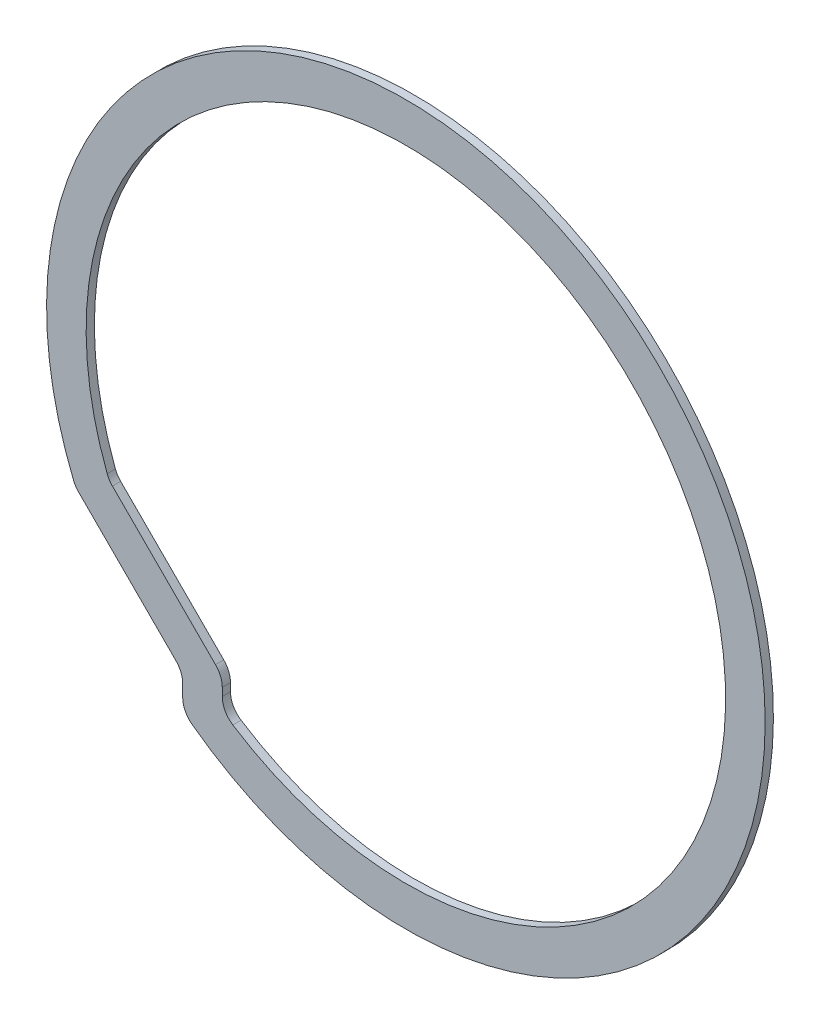
SolidWorks part; units mm, degrees
material "Balsa"
ref_plane "Front Plane" through (0, 0, 0) normal (0, 0, 1) x (1, 0, 0)
ref_plane "Top Plane" through (0, 0, 0) normal (0, 1, 0) x (1, 0, 0)
ref_plane "Right Plane" through (0, 0, 0) normal (1, 0, 0) x (0, 0, -1)
sketch "Sketch1" plane through (0, 0, 0) normal (0, 0, 1) x (1, 0, 0)
  line L0 (0, 32.094) -> (0, -346.2619) construction
  line L1 (0, 0) -> (0, 244.345) construction
  line L2 (0, 0) -> (0, 471.6969) construction
  line L3 (0, 0) -> (-283.5939, 0) construction
  line L4 (-127.2933, -32.5553) -> (-85.9841, -73.8644)
  line L5 (-85.9841, -73.8644) -> (-85.9841, -86.6438)
  line L6 (-85.9841, -73.8644) -> (-54.3993, -105.4493) construction
  arc A0 (-54.3993, -105.4493) -> (-127.2933, -32.5553) centre (0, 21.844) ccw
  arc A2 (-82.075, -89.6305) -> (-54.3993, -105.4493) centre (0, 21.844) ccw construction
  arc A3 (-127.2933, -32.5553) -> (-82.075, -89.6305) centre (0, 21.844) ccw construction
  arc A4 (-85.9841, -86.6438) -> (-54.3993, -105.4493) centre (0, 21.844) ccw
  spline S2 degree 3 poles (-1530.9406, -7642.7149) (259.0907, -1408.3953) (378.6573, 10.519) (49.9381, 150.9258) (45.7097, 152.4909) (37.1079, 155.2035) (32.7346, 156.3511) (27.1752, 157.5183) (26.0587, 157.7384) (23.8163, 158.1514) (22.6888, 158.3447) (19.306, 158.8811) (17.0511, 159.1813) (10.2867, 159.9126) (1.2693, 160.4377) (-7.745, 160.0789) (-14.5046, 159.4749) (-16.7575, 159.2176) (-20.1367, 158.7464) (-21.263, 158.5751) (-23.5156, 158.2037) (-24.6421, 158.0036) (-30.2426, 156.9366) (-34.6466, 155.8674) (-43.3063, 153.3113) (-47.562, 151.8242) (-55.9254, 148.4331) (-60.0331, 146.529) (-66.0807, 143.3516) (-68.0818, 142.2359) (-72.0044, 139.9197) (-73.9301, 138.7173) (-79.6017, 134.9792) (-86.884, 129.6473) (-93.6143, 123.6295) (-98.4521, 118.8554) (-100.0296, 117.2204) (-102.3424, 114.7015) (-103.1054, 113.8496) (-104.6077, 112.1297) (-105.3467, 111.2623) (-108.9818, 106.8875) (-111.6981, 103.2683) (-116.7574, 95.7975) (-119.1004, 91.9459) (-123.4121, 84.0098) (-125.3809, 79.9253) (-127.6006, 74.6695) (-128.0327, 73.61) (-128.8681, 71.4874) (-129.2719, 70.423) (-130.4422, 67.2205) (-131.1674, 65.0732) (-133.1812, 58.5951) (-135.4347, 49.861) (-136.834, 40.9354) (-137.5569, 34.168) (-137.7434, 31.9) (-137.9397, 28.4793) (-137.9911, 27.3374) (-138.0656, 25.0596) (-138.0887, 23.9223) (-138.135, 18.2442) (-137.9496, 13.7276) (-137.1441, 4.7454) (-136.5239, 0.2797) (-134.8456, -8.6005) (-133.7876, -13.015) (-131.2181, -21.791) (-129.7278, -26.0794) (-126.351, -34.4622) (-124.4643, -38.5569) (-120.2966, -46.5538) (-118.0156, -50.456) (-114.9122, -55.2108) (-114.2789, -56.1556) (-112.9868, -58.0327) (-112.3272, -58.9661) (-110.315, -61.7398) (-108.9333, -63.5482) (-104.6702, -68.8537) (-98.6716, -75.6089) (-92.0553, -81.7381) (-86.8592, -86.0978) (-85.0881, -87.5114) (-82.3719, -89.5716) (-81.4566, -90.2482) (-79.6058, -91.5811) (-78.6696, -92.238) (312.7351, -359.6403) (1980.7618, 1435.5712) (5240.7041, 5800.1077) knots -2.409432 -2.409432 -2.409432 -2.409432 0.03125 0.03125 0.0625 0.0625 0.09375 0.09375 0.101563 0.101563 0.109375 0.109375 0.125 0.125 0.15625 0.1875 0.1875 0.203125 0.203125 0.210937 0.210937 0.21875 0.21875 0.25 0.25 0.28125 0.28125 0.3125 0.3125 0.328125 0.328125 0.34375 0.34375 0.375 0.40625 0.40625 0.421875 0.421875 0.429687 0.429687 0.4375 0.4375 0.46875 0.46875 0.5 0.5 0.53125 0.53125 0.539062 0.539062 0.546875 0.546875 0.5625 0.5625 0.59375 0.625 0.625 0.640625 0.640625 0.648437 0.648437 0.65625 0.65625 0.6875 0.6875 0.71875 0.71875 0.75 0.75 0.78125 0.78125 0.8125 0.8125 0.84375 0.84375 0.851562 0.851562 0.859375 0.859375 0.875 0.875 0.90625 0.9375 0.9375 0.953125 0.953125 0.960937 0.960937 0.96875 0.96875 4.2021 4.2021 4.2021 4.2021 only from (66.3397, 143.1887) to (-66.0465, -100.0388)
  spline S3 degree 3 poles (66.3397, 143.1887) (62.3323, 145.3909) (58.2494, 147.3758) (49.9381, 150.9258) (45.7097, 152.4909) (37.1079, 155.2035) (32.7346, 156.3511) (27.1752, 157.5183) (26.0587, 157.7384) (23.8163, 158.1514) (22.6888, 158.3447) (19.306, 158.8811) (17.0511, 159.1813) (10.2867, 159.9126) (1.2693, 160.4377) (-7.745, 160.0789) (-14.5046, 159.4749) (-16.7575, 159.2176) (-20.1367, 158.7464) (-21.263, 158.5751) (-23.5156, 158.2037) (-24.6421, 158.0036) (-30.2426, 156.9366) (-34.6466, 155.8674) (-43.3063, 153.3113) (-47.562, 151.8242) (-55.9254, 148.4331) (-60.0331, 146.529) (-66.0807, 143.3516) (-68.0818, 142.2359) (-72.0044, 139.9197) (-73.9301, 138.7173) (-79.6017, 134.9792) (-86.884, 129.6473) (-93.6143, 123.6295) (-98.4521, 118.8554) (-100.0296, 117.2204) (-102.3424, 114.7015) (-103.1054, 113.8496) (-104.6077, 112.1297) (-105.3467, 111.2623) (-108.9818, 106.8875) (-111.6981, 103.2683) (-116.7574, 95.7975) (-119.1004, 91.9459) (-123.4121, 84.0098) (-125.3809, 79.9253) (-127.6006, 74.6695) (-128.0327, 73.61) (-128.8681, 71.4874) (-129.2719, 70.423) (-130.4422, 67.2205) (-131.1674, 65.0732) (-133.1812, 58.5951) (-135.4347, 49.861) (-136.834, 40.9354) (-137.5569, 34.168) (-137.7434, 31.9) (-137.9397, 28.4793) (-137.9911, 27.3374) (-138.0656, 25.0596) (-138.0887, 23.9223) (-138.135, 18.2442) (-137.9496, 13.7276) (-137.1441, 4.7454) (-136.5239, 0.2797) (-134.8456, -8.6005) (-133.7876, -13.015) (-131.2181, -21.791) (-129.7278, -26.0794) (-127.6847, -31.1513) (-127.3213, -32.0275) (-126.9491, -32.8995) knots 0 0 0 0 0.03125 0.03125 0.0625 0.0625 0.09375 0.09375 0.101563 0.101563 0.109375 0.109375 0.125 0.125 0.15625 0.1875 0.1875 0.203125 0.203125 0.210937 0.210937 0.21875 0.21875 0.25 0.25 0.28125 0.28125 0.3125 0.3125 0.328125 0.328125 0.34375 0.34375 0.375 0.40625 0.40625 0.421875 0.421875 0.429687 0.429687 0.4375 0.4375 0.46875 0.46875 0.5 0.5 0.53125 0.53125 0.539062 0.539062 0.546875 0.546875 0.5625 0.5625 0.59375 0.625 0.625 0.640625 0.640625 0.648437 0.648437 0.65625 0.65625 0.6875 0.6875 0.71875 0.71875 0.75 0.75 0.78125 0.78125 0.787815 0.787815 0.787815 0.787815 construction
  point P2 (0, 160.2226)
  point P3 (0, -116.9127)
  point P23 (-85.9841, -73.8644)
  dimension "D1" = 277.1353
  dimension "D2" = 276.86
  dimension "D3" = 21.844
  dimension "D5" = 45
  dimension "D6" = 113.03
  dimension "D4" = 58.42
  dimension "D7" = 45
extrude "Boss-Extrude1" add sketch "Sketch1" along normal mid plane 3.175
sketch "Sketch2" plane through (0, 0, 1.5875) normal (0, 0, 1) x (1, 0, 0)
  line L4 (-114.3729, -23.9231) -> (-70.7441, -67.5518)
  line L5 (-70.7441, -67.5518) -> (-70.7441, -79.0076)
  line L6 (-114.3729, -23.9231) -> (-70.7441, -67.5518)
  line L7 (-70.7441, -67.5518) -> (-70.7441, -79.0076)
  arc A2 (-70.7441, -79.0076) -> (-114.3729, -23.9231) centre (0, 21.844) ccw
  arc A3 (-70.7441, -79.0076) -> (-114.3729, -23.9231) centre (0, 21.844) ccw
  dimension "D1" = 15.24
extrude "Cut-Extrude1" cut sketch "Sketch2" against normal up to surface (3.175 mm away) up to face at (-27.5361, -9.1994, -1.5875)
fillet "Fillet1" radius 8.89 6 edges at (-127.2933, -32.5553, 0) (-114.3729, -23.9231, 0) (-85.9841, -73.8644, 0) (-85.9841, -86.6438, 0) (-70.7441, -67.5518, 0) (-70.7441, -79.0076, 0)
sketch "Sketch3" plane through (0, 0, 1.5875) normal (0, 0, 1) x (1, 0, 0)
  line L0 (-0.0002, 49.9919) -> (-0.0176, 733.2) construction
  line L1 (-0.0002, 49.9919) -> (-0.0176, 733.2) construction
  line L2 (-136.2041, -28.3557) -> (-0.0002, 49.9919) construction
  line L3 (136.2076, -28.3488) -> (-0.0002, 49.9919) construction
  line L4 (-136.2041, -28.3557) -> (-0.0002, 49.9919) construction
  line L5 (136.2076, -28.3488) -> (-0.0002, 49.9919) construction
  line L6 (-1.6539, 152.6441) -> (-1.654, 160.2641)
  line L7 (1.6481, 152.6442) -> (1.648, 160.2642)
  line L8 (-1.6539, 152.6441) -> (1.6481, 152.6442)
  line L9 (119.8485, -45.962) -> (106.7537, -38.3747)
  line L10 (121.4435, -43.2066) -> (108.3479, -35.6188)
  line L11 (-126.0584, -33.7901) -> (-88.588, -71.2606)
  line L12 (-85.9841, -77.5468) -> (-85.9841, -82.2574)
  line L13 (-126.0584, -33.7901) -> (-88.588, -71.2606) construction
  line L14 (-85.9841, -77.5468) -> (-85.9841, -82.2574) construction
  line L18 (121.4435, -43.2066) -> (108.3479, -35.6188)
  line L30 (-123.167, -47.8929) -> (-106.3545, -38.1503)
  line L35 (119.8485, -45.962) -> (106.7537, -38.3747)
  line L47 (108.5244, -35.721) -> (120.1169, -46.1175) construction
  line L48 (114.3206, -40.9193) -> (126.5619, -48.0121) construction
  line L49 (113.8577, -42.5592) -> (122.0137, -47.2849)
  line L50 (115.5132, -39.7021) -> (123.6691, -44.4278)
  line L51 (113.8577, -42.5592) -> (115.5132, -39.7021)
  line L52 (122.0137, -47.2849) -> (123.6691, -44.4278)
  line L58 (-124.7703, -45.1423) -> (-107.9499, -35.3951)
  line L59 (-124.7703, -45.1423) -> (-123.167, -47.8929)
  line L71 (-124.7703, -45.1423) -> (-123.167, -47.8929) construction
  line L72 (-124.7703, -45.1423) -> (-107.9499, -35.3951) construction
  line L73 (-123.167, -47.8929) -> (-106.3545, -38.1503) construction
  line L74 (-123.167, -47.8929) -> (-107.9499, -35.3951) construction
  line L75 (-115.5584, -41.644) -> (-110.9064, -38.9482) construction
  line L76 (-119.3826, -41.9518) -> (-112.6266, -38.0369)
  line L77 (-117.727, -44.8088) -> (-110.971, -40.8938)
  line L78 (-119.3826, -41.9518) -> (-117.727, -44.8088)
  line L79 (-112.6266, -38.0369) -> (-110.971, -40.8938)
  arc A0 (-54.3993, -105.4493) -> (-127.2933, -32.5553) centre (0, 21.844) ccw construction
  arc A2 (-1.654, 160.2641) -> (-130.2816, -24.9489) centre (0, 21.844) ccw construction
  arc A3 (-130.2816, -24.9489) -> (-127.2933, -32.5553) centre (0, 21.844) ccw construction
  arc A4 (-1.654, 160.2641) -> (-130.2816, -24.9489) centre (0, 21.844) ccw construction
  arc A5 (-130.2816, -24.9489) -> (-127.9919, -30.8906) centre (0, 21.844) ccw construction
  arc A6 (-82.3849, -89.4016) -> (-127.9919, -30.8906) centre (0, 21.844) ccw
  arc A7 (-127.9919, -30.8906) -> (-126.0584, -33.7901) centre (-119.7722, -27.504) ccw
  arc A8 (-85.9841, -77.5468) -> (-88.588, -71.2606) centre (-94.8741, -77.5468) ccw
  arc A9 (-85.9841, -82.2574) -> (-82.3849, -89.4016) centre (-77.0941, -82.2574) ccw
  arc A11 (-127.9919, -30.8906) -> (-126.0584, -33.7901) centre (-119.7722, -27.504) ccw construction
  arc A12 (-85.9841, -77.5468) -> (-88.588, -71.2606) centre (-94.8741, -77.5468) ccw construction
  arc A13 (-85.9841, -82.2574) -> (-82.3849, -89.4016) centre (-77.0941, -82.2574) ccw construction
  arc A14 (130.2841, -24.9419) -> (1.648, 160.2642) centre (0, 21.844) ccw construction
  arc A15 (1.648, 160.2642) -> (-1.654, 160.2641) centre (0, 21.844) ccw
  arc A16 (130.2841, -24.9419) -> (1.648, 160.2642) centre (0, 21.844) ccw construction
  arc A17 (1.648, 160.2642) -> (-1.654, 160.2641) centre (0, 21.844) ccw
  spline S0 degree 3 poles (106.7537, -38.3747) (107.2851, -37.456) (107.8165, -36.5374) (108.3479, -35.6188) knots 0 0 0 0 1 1 1 1 weights 1 1 1 1
  spline S1 degree 3 poles (119.8485, -45.962) (120.3802, -45.0435) (120.9118, -44.1251) (121.4435, -43.2066) knots 0 0 0 0 1 1 1 1 weights 1 1 1 1
  spline S2 degree 3 poles (-885.9096, -1769.7959) (-211.5315, -623.0099) (457.4335, 532.6653) (1115.294, 1687.3986) knots -628.025755 -628.025755 -628.025755 -628.025755 629.32196 629.32196 629.32196 629.32196 weights 1.00213 0.999289 0.99929 1.002132 only from (119.8485, -45.962) to (121.4435, -43.2066)
  spline S3 degree 3 poles (-1103.1887, 1695.5005) (-443.6401, 540.3172) (225.3723, -615.0907) (899.402, -1763.0447) knots -628.279881 -628.279881 -628.279881 -628.279881 629.068312 629.068312 629.068312 629.068312 weights 1.001665 0.999445 0.999445 1.001664 only from (-107.9499, -35.3951) to (-106.3545, -38.1503)
  spline S4 degree 3 poles (-107.9499, -35.3951) (-107.4181, -36.3135) (-106.8863, -37.2319) (-106.3545, -38.1503) knots 0 0 0 0 1 1 1 1 weights 1 1 1 1 construction
  spline S6 degree 3 poles (-898.3985, -1763.0369) (-224.3104, -615.0446) (444.2624, 540.7506) (1102.1878, 1695.4772) knots -627.922228 -627.922228 -627.922228 -627.922228 629.425892 629.425892 629.425892 629.425892 weights 1.001921 0.999359 0.99936 1.001924 only from (106.7537, -38.3747) to (108.3479, -35.6188)
  point P49 (-116.0256, -43.8229)
  point P50 (120.451, -46.3794)
  arc M19 (-82.3849, -89.4016) -> (-127.9919, -30.8906) centre (0, 21.844) ccw
  line M21 (-126.0584, -33.7901) -> (-88.588, -71.2606)
  dimension "D1" = 3.302
  dimension "D2" = 7.62
  dimension "D4" = 3.302
  dimension "D5" = 7.62
  dimension "D6" = 3.302
  dimension "D7" = 5.842
  dimension "D3" = 0
extrude "Cut-Extrude2" [suppressed] cut sketch "Sketch3" against normal through all contours L79 L76 L77 M21 | L6 L8 L7 M19 | L51 L49 L50 M19
equation "\"a\"= 0.06"
equation "\"slotwidth\"=0.13"
equation "\"slotheight\"=0.3"
